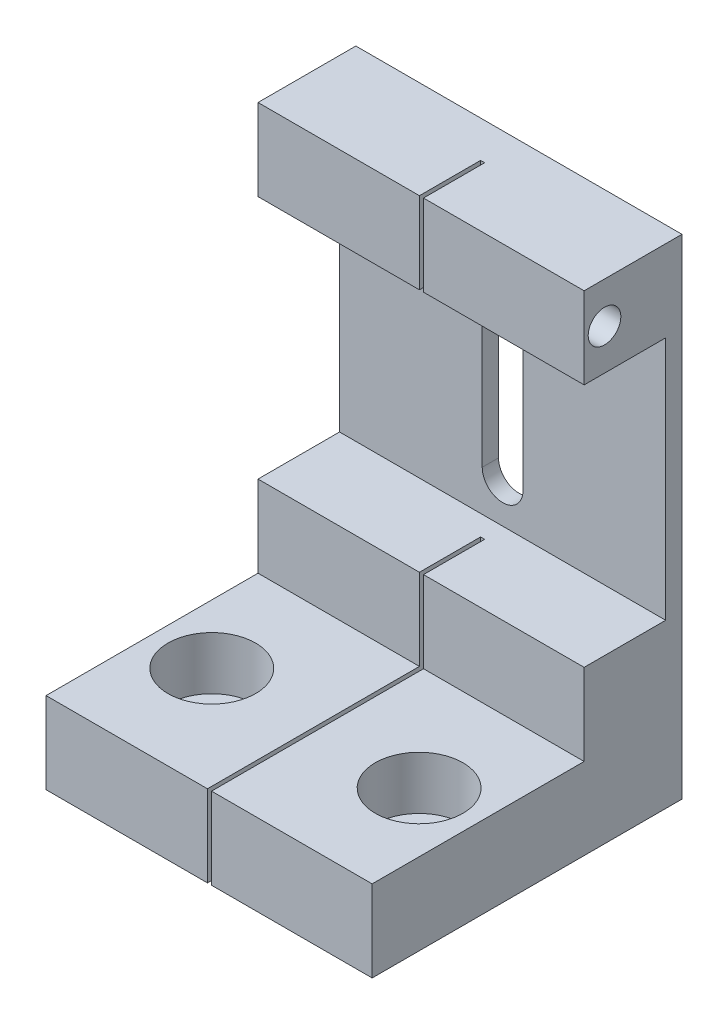
SolidWorks part; units mm, degrees
ref_plane "Front Plane" through (0, 0, 0) normal (0, 0, 1) x (1, 0, 0)
ref_plane "Top Plane" through (0, 0, 0) normal (0, 1, 0) x (1, 0, 0)
ref_plane "Right Plane" through (0, 0, 0) normal (1, 0, 0) x (0, 0, -1)
sketch "Sketch1" plane through (0, 0, 0) normal (0, 0, 1) x (1, 0, 0)
  line L1 (0, 0) -> (-40, 0)
  line L2 (0, 0) -> (0, -60)
  line L3 (0, -60) -> (-40, -60)
  line L4 (-40, 0) -> (-40, -60)
  dimension "D1" = 40
  dimension "D2" = 60
extrude "Boss-Extrude1" add sketch "Sketch1" along normal blind 12
sketch "Sketch2" plane through (0, 0, 12) normal (0, 0, 1) x (1, 0, 0)
  line L0 (-20, -15) -> (-20, -35) construction
  line L1 (-17.5, -15) -> (-17.5, -35)
  line L2 (-22.5, -15) -> (-22.5, -35)
  line L4 (-40, -60) -> (0, -60) construction
  line L5 (0, 0) -> (-40, 0) construction
  line L6 (-20, 0) -> (-20, -5.6142) construction
  arc A0 (-17.5, -15) -> (-22.5, -15) centre (-20, -15) ccw
  arc A1 (-22.5, -35) -> (-17.5, -35) centre (-20, -35) ccw
  point P2 (-20, -25)
  dimension "D1" = 5
  dimension "D2" = 20
  dimension "D4" = 35
extrude "Cut-Extrude1" cut sketch "Sketch2" against normal through all
sketch "Sketch5" plane through (0, 0, 0) normal (1, 0, 0) x (0, 0, -1)
  line L0 (-2, -10) -> (-12, -10)
  line L1 (-12, -60) -> (-12, 0) construction
  line L2 (-2, -10) -> (-2, -40)
  line L3 (-12, -60) -> (0, -60) construction
  line L4 (-2, -40) -> (-12, -40)
  line L7 (-12, -10) -> (-12, -40)
  dimension "D1" = 10
  dimension "D4" = 30
  dimension "D5" = 20
extrude "Cut-Extrude4" cut sketch "Sketch5" against normal through all
sketch "Sketch6" plane through (0, 0, 12) normal (0, 0, 1) x (1, 0, 0)
  line L0 (-40, -40) -> (-40, -60) construction
  line L1 (0, -60) -> (-40, -60)
  line L2 (0, -60) -> (0, -50)
  line L3 (0, -50) -> (-40, -50)
  line L4 (-40, -60) -> (-40, -50)
  dimension "D1" = 10
extrude "Boss-Extrude2" add sketch "Sketch6" along normal blind 26
sketch "Sketch7" plane through (0, -50, 0) normal (0, 1, 0) x (1, 0, 0)
  line L3 (-40, -38) -> (-40, -12) construction
  circle A0 centre (-4.0875, -15.1829) radius 2
  circle A1 centre (-35.875, -15.1829) radius 2
  dimension "D1" = 4
  dimension "D2" = 4
  dimension "D3" = 4.125
  dimension "D5" = 31.7875
extrude "Cut-Extrude5" [suppressed] cut sketch "Sketch7" against normal blind 40
sketch "Sketch8" plane through (0, 0, 0) normal (0, 1, 0) x (1, 0, 0)
  line L0 (-40, -12) -> (0, -12) construction
  line L2 (-20.2, -38) -> (-19.7, -38)
  line L5 (-20.2, -38) -> (-20.2, -4.5)
  line L7 (0, -38) -> (-40, -38) construction
  line L9 (-20.2, -4.5) -> (-19.7, -4.5)
  line L10 (-19.7, -38) -> (-19.7, -4.5)
  line L11 (-22.5, 0) -> (-22.5, -2) construction
  dimension "D1" = 0.5
  dimension "D2" = 2.3
  dimension "D3" = 7.5
extrude "Cut-Extrude7" cut sketch "Sketch8" against normal up to surface (60 mm away) up to face at (-20, -60, 19)
sketch "Sketch9" plane through (0, -60, 0) normal (0, -1, 0) x (1, 0, 0)
  line L3 (0, 38) -> (0, 0) construction
  line L5 (-40, 2) -> (0, 2) construction
  circle A0 centre (-32.73, 0) radius 2
  circle A1 centre (-7.3, 0) radius 2
  dimension "D1" = 4
  dimension "D3" = 7.3
  dimension "D4" = 4
  dimension "D2" = 25.43
extrude "Cut-Extrude9" [suppressed] cut sketch "Sketch9" against normal blind 15
sketch "Sketch10" plane through (0, 0, 0) normal (1, 0, 0) x (0, 0, -1)
  line L1 (-12, 0) -> (0, 0) construction
  line L2 (-12, -10) -> (-12, 0) construction
  circle A0 centre (-9.5, -5) radius 2
  dimension "D1" = 4
  dimension "D2" = 5
  dimension "D3" = 2.5
extrude "Cut-Extrude10" cut sketch "Sketch10" against normal blind 30
sketch "Sketch12" plane through (0, -60, 0) normal (0, -1, 0) x (1, 0, 0)
  line L0 (-32.73, 24.94) -> (-32.73, -0.49) construction
  line L1 (-32.73, -0.49) -> (-7.3, -0.49) construction
  line L2 (-7.3, -0.49) -> (-7.3, 24.94) construction
  line L3 (-7.3, 24.94) -> (-32.73, 24.94) construction
  line L4 (-40, 2) -> (0, 2) construction
  line L6 (0, 38) -> (0, 0) construction
  line L10 (-19.7, 38) -> (0, 38) construction
  line L11 (-40, 0) -> (-40, 38) construction
  circle A0 centre (-7.3, 24.94) radius 3.4
  circle A1 centre (-32.73, 24.94) radius 3.4
  circle A2 centre (-32.73, -0.49) radius 2.49
  circle A3 centre (-7.3, -0.49) radius 2.49
  circle A4 centre (-7.3, 24.94) radius 5.375 construction
  circle A5 centre (-32.73, -0.46) radius 3.4 [skipped]
  circle A6 centre (-7.3, -0.46) radius 3.4 [skipped]
  dimension "D1" = 6.8
  dimension "D2" = 2
  dimension "D3" = 2
  dimension "D4" = 10.75
  dimension "D6" = 7.3
  dimension "D7" = 25.43
  dimension "D8" = 4.98
  dimension "D9" = 25.43
  dimension "D11" = 13.06
  dimension "D5" = 2
  dimension "D12" = 7.27
extrude "Cut-Extrude13" cut sketch "Sketch12" against normal up to surface (10 mm away) up to face at (-9.85, -50, 25)
sketch "Sketch14" plane through (0, -50, 0) normal (0, 1, 0) x (1, 0, 0)
  line L0 (-32.73, -24.94) -> (18.13, -24.94) construction
  circle A0 centre (-32.73, -24.94) radius 5.375
  circle A1 centre (-7.3, -24.94) radius 5.375
  dimension "D1" = 10.75
  dimension "D3" = 25.43
  dimension "D2" = 2
extrude "Cut-Extrude14" cut sketch "Sketch14" against normal blind 6.5
equation "\"inch\"= 25.43"
equation "\"D5@Sketch7\"=\"inch\"*1.25"
equation "\"D2@Sketch9\"=\"inch\""
equation "\"D7@Sketch12\"=\"inch\""
equation "\"D9@Sketch12\"=\"inch\""
equation "\"D3@Sketch14\"=\"inch\""
